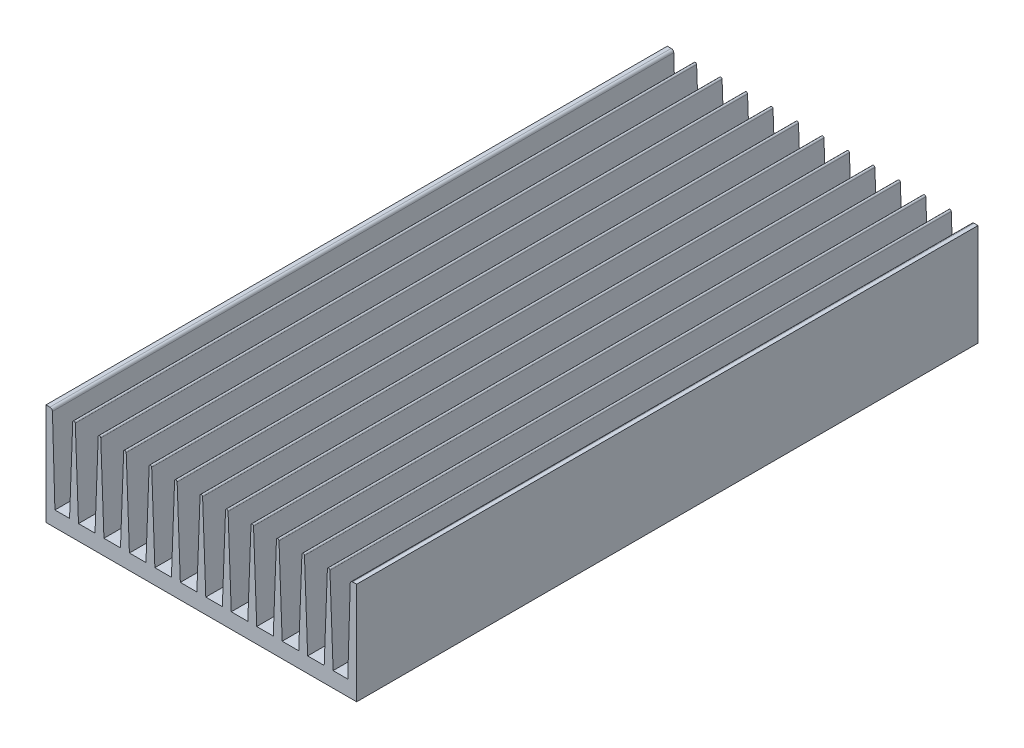
SolidWorks part; units mm, degrees
ref_plane "Спереди" through (0, 0, 0) normal (0, 0, 1) x (1, 0, 0)
ref_plane "Сверху" through (0, 0, 0) normal (0, 1, 0) x (1, 0, 0)
ref_plane "Справа" through (0, 0, 0) normal (1, 0, 0) x (0, 0, -1)
sketch "Эскиз1" plane through (0, 0, 0) normal (0, 0, 1) x (1, 0, 0)
  line L0 (0, 40) -> (1.529, 40)
  line L1 (0, 0) -> (122, 0)
  line L2 (2.5285, 39.0294) -> (3.5, 6)
  line L3 (0, 40) -> (0, 0)
  line L4 (122, 40) -> (122, 0)
  line L5 (61, 63.7127) -> (61, -22.2582) construction
  line L8 (122, 40) -> (120.471, 40)
  line L9 (119.4715, 39.0294) -> (118.5, 6)
  line L10 (3.5, 6) -> (118.5, 6)
  arc A0 (1.529, 40) -> (2.5285, 39.0294) centre (1.529, 39) cw
  arc A2 (120.471, 40) -> (119.4715, 39.0294) centre (120.471, 39) ccw
  point P18 (119.5, 40)
  dimension "D9" = 1
  dimension "D1" = 122
  dimension "D2" = 6
  dimension "D3" = 40
  dimension "D4" = 3.5
  dimension "D7" = 2.5
extrude "Вытянуть1" add sketch "Эскиз1" along normal blind 244
sketch "Эскиз2" plane through (0, 0, 244) normal (0, 0, 1) x (1, 0, 0)
  line L0 (118.5, 6) -> (3.5, 6) construction
  line L1 (10.5, 39.5) -> (9.25, 6)
  line L2 (11, 39.5) -> (11, 22.5548) construction
  line L3 (11.5, 39.5) -> (12.75, 6)
  line L4 (9.25, 6) -> (12.75, 6)
  line L6 (0, 40) -> (0, 0) construction
  arc A0 (10.5, 39.5) -> (11.5, 39.5) centre (11, 39.5) cw
  dimension "D1" = 34
  dimension "D3" = 0.5
  dimension "D2" = 3.5
  dimension "D4" = 11
  dimension "D5" = 1
extrude "Вытянуть3" add sketch "Эскиз2" against normal blind 244
pattern_curve "Кривая1" of "Вытянуть3" along edge at (61, 0, 0) parameters "D1"=11, "D3"=10, "D2"=1, "D4"=50
sketch "Эскиз3" plane through (0, 0, 0) normal (0, -1, 0) x (1, 0, 0)
  line L0 (-14.0506, 236) -> (137.5079, 236) construction
  line L1 (0, 244) -> (122, 244) construction
  line L2 (0, 244) -> (0, 0) construction
  line L3 (-46.7511, 122) -> (151.4312, 122) construction
  line L4 (0, 0) -> (122, 0) construction
  circle A0 centre (26, 236) radius 2.25
  circle A1 centre (96, 236) radius 2.25
  circle A2 centre (96, 8) radius 2.25
  circle A3 centre (26, 8) radius 2.25
  dimension "D2" = 70
  dimension "D4" = 4.5
  dimension "D1" = 8
  dimension "D3" = 26
extrude "Вырез-Вытянуть1" cut sketch "Эскиз3" against normal blind 6
sketch "Эскиз4" plane through (1.488, 0, 27.4005) normal (0, -1, 0) x (1, 0, 0)
  line L0 (60.512, 61.5995) -> (60.512, 196.5995) construction
  line L1 (141.5072, 109.0995) -> (90.1328, 109.0995) construction
  line L2 (120.512, 216.5995) -> (120.512, -27.4005) construction
  line L3 (-1.488, 216.5995) -> (120.512, 216.5995) construction
  circle A0 centre (65.512, 22.5995) radius 2.1
  circle A2 centre (103.512, 109.0995) radius 1.6
  circle A3 centre (60.512, 196.5995) radius 1.6
  circle A4 centre (60.512, 61.5995) radius 1.6
  dimension "D2" = 3.2
  dimension "D4" = 3.2
  dimension "D5" = 4.2
  dimension "D7" = 135
  dimension "D8" = 87.5
  dimension "D9" = 17
  dimension "D1" = 20
  dimension "D10" = 174
  dimension "D6" = 55
  dimension "D3" = 60
extrude "Вырез-Вытянуть2" cut sketch "Эскиз4" against normal blind 6
cosmetic thread "Условное изображение резьбы5" parameters "D2"=5
cosmetic thread "Условное изображение резьбы6" parameters "D2"=4
cosmetic thread "Условное изображение резьбы7" parameters "D2"=4
cosmetic thread "Условное изображение резьбы8" parameters "D2"=4
